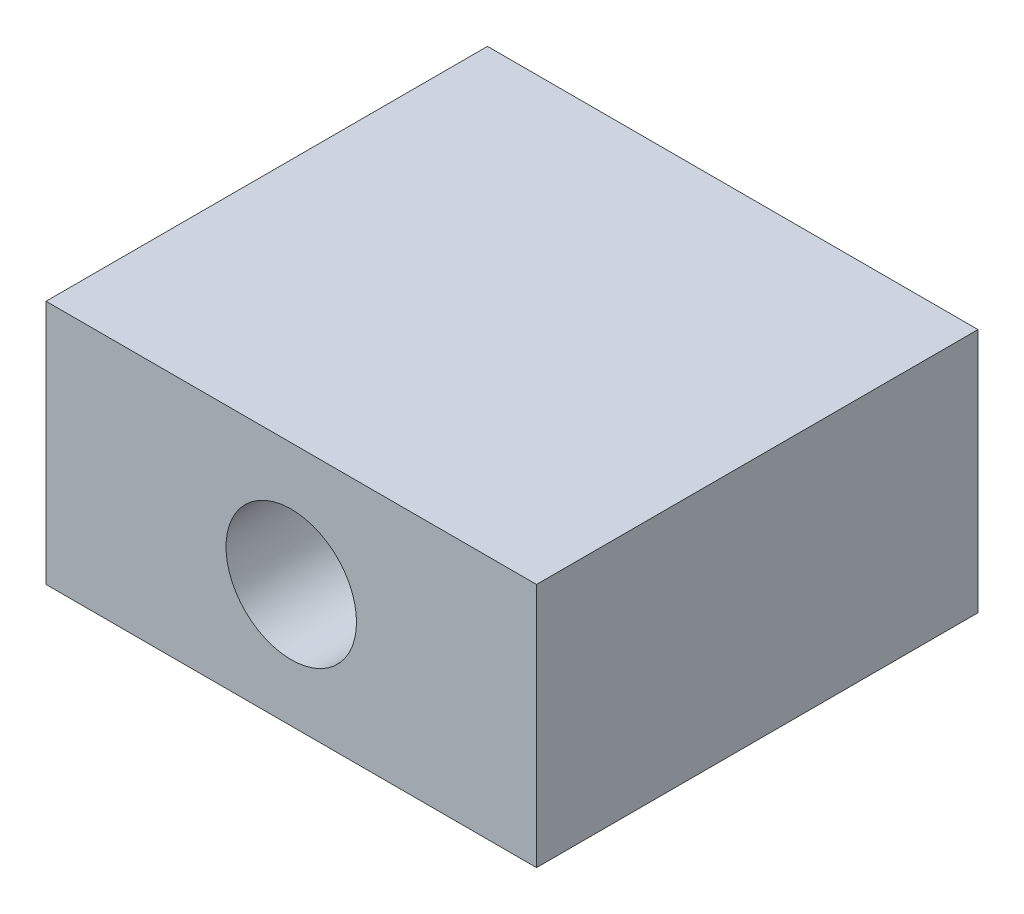
SolidWorks part; units mm, degrees
material "6061-T6 (SS)"
ref_plane "Front Plane" through (0, 0, 0) normal (0, 0, 1) x (1, 0, 0)
ref_plane "Top Plane" through (0, 0, 0) normal (0, 1, 0) x (1, 0, 0)
ref_plane "Right Plane" through (0, 0, 0) normal (1, 0, 0) x (0, 0, -1)
sketch "Sketch1" plane through (0, 0, 0) normal (0, 0, 1) x (1, 0, 0)
  line L1 (-12.7, -6.35) -> (12.7, -6.35)
  line L2 (-12.7, -6.35) -> (-12.7, 6.35)
  line L3 (-12.7, 6.35) -> (12.7, 6.35)
  line L4 (12.7, -6.35) -> (12.7, 6.35)
  line L5 (-12.7, -6.35) -> (12.7, 6.35) construction
  line L6 (-12.7, 6.35) -> (12.7, -6.35) construction
  point P0 (0, 0)
  dimension "D1" = 25.4
  dimension "D2" = 12.7
extrude "Extrude1" add sketch "Sketch1" along normal blind 22.86
sketch "Sketch2" plane through (0, 0, 22.86) normal (0, 0, 1) x (1, 0, 0)
  line L0 (0, 6.35) -> (0, -6.35) construction
  line L1 (12.7, 6.35) -> (-12.7, 6.35) construction
  line L2 (-12.7, -6.35) -> (12.7, -6.35) construction
  point P6 (0, 0)
hole_wizard "1/4 Clearance Hole1" positions "3DSketch1" profile "Sketch4" hole size "1/4" standard "Ansi Inch" end condition through all
sketch3d "3DSketch1"
  point P0 (0, 0, 0)
  point P3 (0, 0, 22.86)
sketch "Sketch4" plane through (0, 0, 22.86) normal (1, 0, 0) x (0, -1, 0)
  line L0 (0, 0) -> (0, 22.86)
  line L1 (0, 22.86) -> (3.3782, 22.86)
  line L2 (3.3782, 22.86) -> (3.3782, 0)
  line L5 (3.3782, 0) -> (0, 0)
  line L11 (0, -6.35) -> (0, 107.95) construction
  dimension "Thru Hole Dia." = 6.7564
  dimension "Thru Hole Depth" = 22.86
